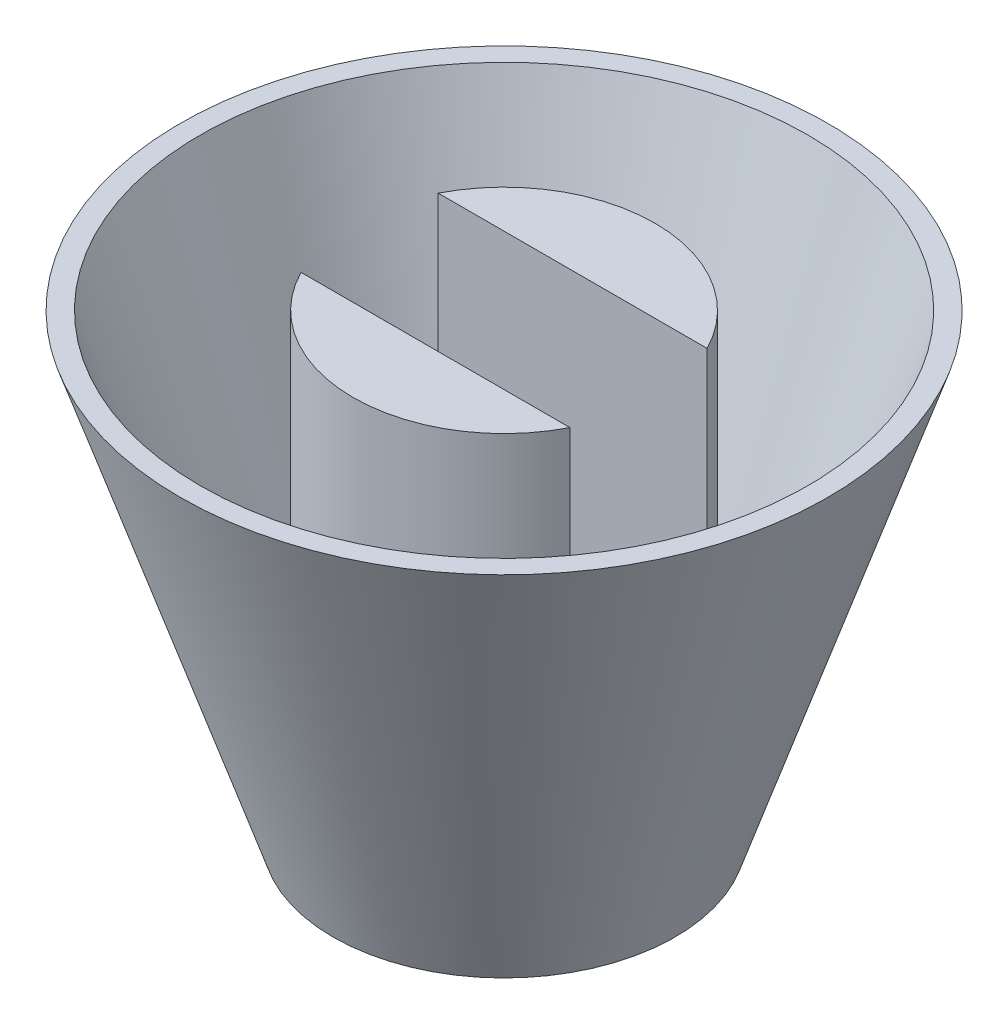
SolidWorks part; units mm, degrees
ref_plane "Front Plane" through (0, 0, 0) normal (0, 0, 1) x (1, 0, 0)
ref_plane "Top Plane" through (0, 0, 0) normal (0, 1, 0) x (1, 0, 0)
ref_plane "Right Plane" through (0, 0, 0) normal (1, 0, 0) x (0, 0, -1)
sketch "Sketch1" plane through (0, 0, 0) normal (0, 1, 0) x (1, 0, 0)
  circle A0 centre (0, 0) radius 42.5
  dimension "D1" = 85
extrude "Boss-Extrude1" add sketch "Sketch1" against normal blind 60 draft 18.485
shell "Shell1" thickness 2.5 removed face at (0, 0, 42.5) removed face at (0, -60, 22.4417)
sketch "Sketch2" plane through (0, -60, 0) normal (0, -1, 0) x (1, 0, 0)
  line L0 (-22.4417, 0) -> (22.4417, 0) construction
  line L2 (-17.6428, 9) -> (17.6428, 9)
  line L3 (-17.6428, -9) -> (17.6428, -9)
  arc A0 (-17.6428, 9) -> (17.6428, 9) centre (0, 0) cw
  circle A1 centre (0, 0) radius 19.8057 construction
  arc A3 (-17.6428, -9) -> (17.6428, -9) centre (0, 0) ccw
  dimension "D1" = 9
extrude "Boss-Extrude2" add sketch "Sketch2" against normal blind 60 separate body
